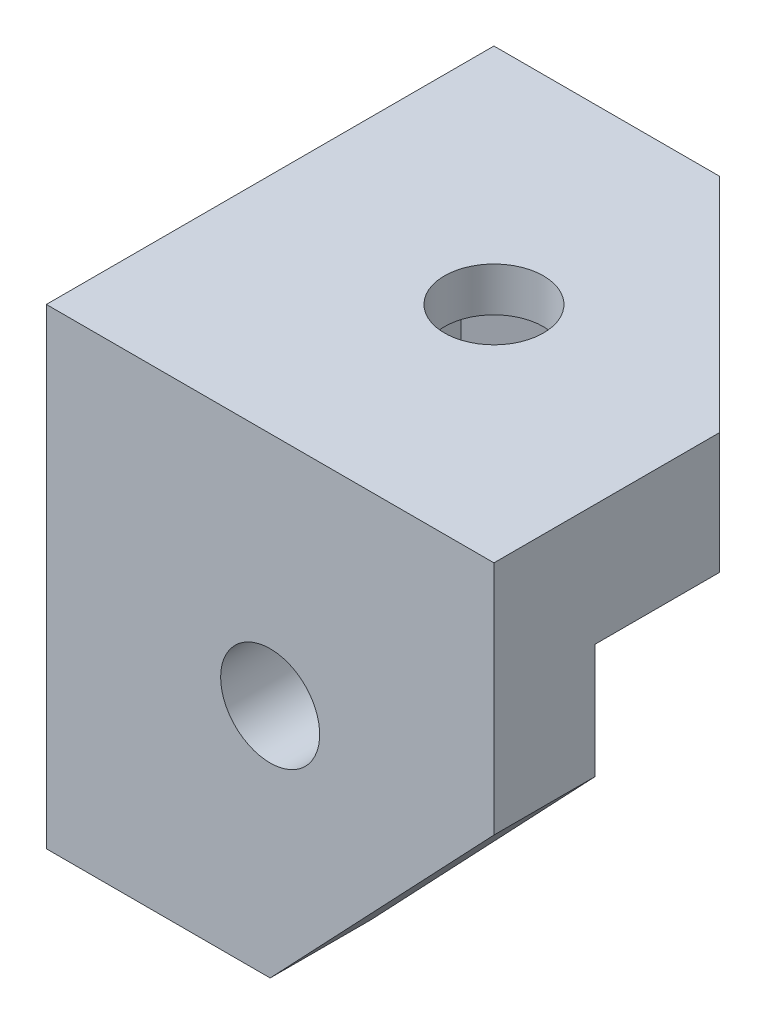
SolidWorks part; units mm, degrees
ref_plane "Front Plane" through (0, 0, 0) normal (0, 0, 1) x (1, 0, 0)
ref_plane "Top Plane" through (0, 0, 0) normal (0, 1, 0) x (1, 0, 0)
ref_plane "Right Plane" through (0, 0, 0) normal (1, 0, 0) x (0, 0, -1)
sketch "Sketch1" plane through (0, 0, 0) normal (0, 1, 0) x (1, 0, 0)
  line L1 (0, 0) -> (32.28, 0)
  line L5 (0, 0) -> (0, 32.28)
  line L6 (0, 32.28) -> (32.28, 32.28)
  line L8 (32.28, 32.28) -> (32.28, 0)
  dimension "D1" = 32.28
extrude "Main Body" add sketch "Sketch1" along normal blind 34
sketch "Sketch3" plane through (0, 0, 0) normal (0, 0, 1) x (1, 0, 0)
  line L0 (0, 0) -> (32.28, 34) construction
  circle A0 centre (16.14, 17) radius 3.5719
  circle A1 centre (16.14, 17) radius 7.9375 construction
  dimension "D1" = 7.1437
  dimension "D2" = 15.875
extrude "9/32 Right Rail" cut sketch "Sketch3" against normal blind 8.3344 and the other way through all
sketch "Sketch4" plane through (0, 0, 0) normal (-1, 0, 0) x (0, 0, 1)
  line L0 (0, 0) -> (-32.28, 34) construction
  circle A0 centre (-16.14, 17) radius 3.5719
  circle A1 centre (-16.14, 17) radius 7.9375 construction
  dimension "D1" = 7.1437
  dimension "D2" = 15.875
extrude "9/32 Left Rail" cut sketch "Sketch4" against normal blind 8.3344
sketch "Sketch8" plane through (0, 34, 0) normal (0, 1, 0) x (1, 0, 0)
  line L0 (0, 0) -> (32.28, 32.28) construction
  circle A0 centre (16.14, 16.14) radius 3.175 construction
  circle A1 centre (16.14, 16.14) radius 7.9375 construction
  circle A2 centre (16.14, 16.14) radius 3.5719
  dimension "D1" = 6.35
  dimension "D2" = 15.875
  dimension "D3" = 0.3969
extrude "9/32 Topper" cut sketch "Sketch8" against normal blind 10 and the other way through all
ref_plane "Plane1" through (5.5562, 0, 0) normal (-1, 0, 0) x (0, 0, 1)
sketch "Sketch9" plane through (0, 0, 0) normal (-1, 0, 0) x (0, 0, 1)
  line L0 (-16.14, 0) -> (-16.14, 34) construction
  line L1 (-9.7242, 17) -> (-12.9321, 22.5563) construction
  line L2 (-12.9321, 22.5563) -> (-19.3479, 22.5563) construction
  line L3 (-19.3479, 22.5563) -> (-22.5558, 17) construction
  line L4 (-22.5558, 17) -> (-19.3479, 11.4438) construction
  line L5 (-19.3479, 11.4438) -> (-12.9321, 11.4438) construction
  line L6 (-12.9321, 11.4438) -> (-9.7242, 17) construction
  line L7 (-32.28, 0) -> (0, 0) construction
  line L8 (-32.28, 34) -> (0, 34) construction
  line L9 (-19.4052, 22.6555) -> (-22.6704, 17)
  line L10 (-22.6704, 17) -> (-19.4052, 11.3445)
  line L11 (-19.4052, 11.3445) -> (-12.8748, 11.3445)
  line L12 (-12.8748, 11.3445) -> (-9.6096, 17)
  line L13 (-9.6096, 17) -> (-12.8748, 22.6555)
  line L14 (-12.8748, 22.6555) -> (-19.4052, 22.6555)
  line L15 (-32.28, 27.65) -> (-32.28, 6.35) construction
  line L16 (-32.28, 34) -> (-32.28, 0) construction
  line L17 (-32.28, 6.35) -> (-5.5562, 6.35) construction
  line L18 (-5.5562, 6.35) -> (-5.5562, 27.65) construction
  line L19 (-5.5562, 27.65) -> (-32.28, 27.65) construction
  line L20 (0, 34) -> (0, 0) construction
  circle A0 centre (-16.14, 17) radius 5.5563 construction
  point P15 (-16.14, 17)
  point P27 (-32.28, 17)
  point P29 (-32.28, 17)
  dimension "D1" = 11.1125
  dimension "D3" = 5.5562
  dimension "D4" = 6.35
  dimension "D2" = 0.0992
extrude "Hex Hole Right" [suppressed] cut sketch "Sketch9" against normal up to surface (26.7238 mm away) from surface up to face at (32.28, 17, -16.14) starting at plane "Plane1"
ref_plane "Plane2" through (0, 0, -5.5563) normal (0, 0, 1) x (1, 0, 0)
sketch "Sketch10" plane through (0, 0, 0) normal (0, 0, 1) x (1, 0, 0)
  line L0 (16.14, 0) -> (16.14, 34) construction
  line L1 (0, 0) -> (32.28, 0) construction
  line L2 (0, 34) -> (32.28, 34) construction
  line L3 (12.8748, 22.6555) -> (9.6096, 17)
  line L4 (22.5558, 17) -> (19.3479, 22.5562) construction
  line L5 (19.3479, 22.5562) -> (12.9321, 22.5562) construction
  line L6 (12.9321, 22.5562) -> (9.7242, 17) construction
  line L13 (9.7242, 17) -> (12.9321, 11.4438) construction
  line L14 (12.9321, 11.4438) -> (19.3479, 11.4438) construction
  line L15 (19.3479, 11.4438) -> (22.5558, 17) construction
  line L16 (9.6096, 17) -> (12.8748, 11.3445)
  line L17 (12.8748, 11.3445) -> (19.4052, 11.3445)
  line L18 (19.4052, 11.3445) -> (22.6704, 17)
  line L19 (22.6704, 17) -> (19.4052, 22.6555)
  line L20 (19.4052, 22.6555) -> (12.8748, 22.6555)
  circle A0 centre (16.14, 17) radius 5.5563 construction
  dimension "D1" = 11.1125
  dimension "D2" = 0.0992
extrude "Hex Hole Left" [suppressed] cut sketch "Sketch10" against normal up to surface (26.7238 mm away) from surface up to face at (16.14, 17, -32.28) starting at plane "Plane2"
sketch "Sketch13" plane through (0, 34, 0) normal (0, 1, 0) x (1, 0, 0)
  line L2 (32.28, 7.2926) -> (7.2926, 7.2926)
  line L3 (7.2926, 32.28) -> (7.2926, 7.2926)
  line L5 (32.28, 4.8617) -> (7.2926, 4.8617) construction
  line L7 (32.28, 32.28) -> (0, 32.28) construction
  line L8 (32.28, 0) -> (32.28, 32.28) construction
  line L9 (7.2926, 32.28) -> (32.28, 32.28)
  line L10 (32.28, 32.28) -> (32.28, 7.2926)
  line L11 (7.2926, 4.8617) -> (7.2926, 0) construction
  line L12 (0, 0) -> (32.28, 0) construction
  point P2 (11.1125, 5.5563)
  point P9 (32.28, 5.5563)
  dimension "D1" = 2.4309
  dimension "D2" = 4.8617
ref_plane "Plane4" through (0, 17, 0) normal (0, 1, 0) x (1, 0, 0)
extrude "Inner Cavity" cut sketch "Sketch13" along direction (0, -1, 0) on the side of the normal offset from surface 8.7312 and the other way up to surface (34 mm away) from surface up to face at (16.14, 34, -19.7119) other way up to face at (16.14, 0, -16.14) starting at plane "Plane4"
sketch "Sketch14" plane through (0, 34, 0) normal (0, 1, 0) x (1, 0, 0)
  line L0 (32.28, 0) -> (0, 32.28) construction
  line L1 (21.7955, 19.4052) -> (16.14, 22.6704)
  line L2 (21.6962, 19.3479) -> (16.14, 22.5558) construction
  line L3 (16.14, 22.5558) -> (10.5838, 19.3479) construction
  line L4 (10.5838, 19.3479) -> (10.5838, 12.9321) construction
  line L5 (10.5838, 12.9321) -> (16.14, 9.7242) construction
  line L6 (16.14, 9.7242) -> (21.6963, 12.9321) construction
  line L7 (21.6963, 12.9321) -> (21.6962, 19.3479) construction
  line L8 (16.14, 22.6704) -> (10.4845, 19.4052)
  line L9 (10.4845, 19.4052) -> (10.4845, 12.8748)
  line L10 (10.4845, 12.8748) -> (16.14, 9.6096)
  line L11 (16.14, 9.6096) -> (21.7955, 12.8748)
  line L12 (21.7955, 12.8748) -> (21.7955, 19.4052)
  line L14 (32.28, 32.28) -> (32.28, 7.2926) construction
  circle A0 centre (16.14, 16.14) radius 5.5562 construction
  dimension "D1" = 11.1125
  dimension "D2" = 0.0992
extrude "Hex Hole Top" cut sketch "Sketch14" along normal offset from surface (13.825 mm away) 3.175 from surface up to face at (16.14, 34, -19.7119) starting at plane "Plane4"
sketch "Sketch16" plane through (0, 34, 0) normal (0, 1, 0) x (1, 0, 0)
  line L0 (32.28, 32.28) -> (16.2767, 32.28)
  line L1 (32.28, 32.28) -> (0, 32.28) construction
  line L2 (16.2767, 32.28) -> (32.28, 16.2767)
  line L3 (32.28, 16.2767) -> (32.28, 32.28)
  line L4 (32.28, 0) -> (32.28, 32.28) construction
  circle A2 centre (16.14, 16.14) radius 3.5719 construction
  dimension "D1" = 7.9375
extrude "Top Corner" cut sketch "Sketch16" against normal up to next
sketch "Sketch17" plane through (0, 0, 0) normal (0, -1, 0) x (1, 0, 0)
  line L0 (32.28, -3.6463) -> (0, -3.6463) construction
  line L1 (32.28, 0) -> (32.28, -7.2926) construction
  line L2 (0, -32.28) -> (0, 0) construction
  line L3 (7.2926, -32.28) -> (0, -32.28) construction
  line L4 (3.6463, -32.28) -> (3.6463, 0) construction
  line L5 (0, 0) -> (32.28, 0) construction
  line L6 (4.44, -16.9337) -> (4.44, -15.3463) construction
  line L7 (16.9338, -2.8525) -> (15.3463, -2.8525)
  line L8 (16.9338, -2.8525) -> (16.9338, -4.44)
  line L9 (16.9338, -4.44) -> (15.3463, -4.44)
  line L10 (15.3463, -2.8525) -> (15.3463, -4.44)
  line L11 (16.9338, -2.8525) -> (15.3463, -4.44) construction
  line L12 (16.9338, -4.44) -> (15.3463, -2.8525) construction
  line L13 (4.44, -13.7588) -> (2.8525, -13.7588)
  line L14 (4.44, -13.7588) -> (4.44, -15.3463)
  line L15 (4.44, -15.3463) -> (2.8525, -15.3463)
  line L16 (2.8525, -13.7588) -> (2.8525, -15.3463)
  line L17 (4.44, -13.7588) -> (2.8525, -15.3463) construction
  line L18 (4.44, -15.3463) -> (2.8525, -13.7588) construction
  line L19 (4.44, -16.9337) -> (2.8525, -16.9337)
  line L20 (4.44, -16.9337) -> (4.44, -18.5213)
  line L21 (4.44, -18.5213) -> (2.8525, -18.5213)
  line L22 (2.8525, -16.9337) -> (2.8525, -18.5213)
  line L23 (4.44, -16.9337) -> (2.8525, -18.5213) construction
  line L24 (4.44, -18.5213) -> (2.8525, -16.9337) construction
  point P12 (16.14, -3.6463)
  point P17 (3.6463, -14.5525)
  point P22 (3.6463, -17.7275)
  point P27 (16.14, -3.6463)
  point P28 (3.6463, -16.14)
  point P29 (4.44, -16.14)
  dimension "D1" = 1.5875
  dimension "D2" = 1.5875
extrude "Cut-Extrude1" [suppressed] cut sketch "Sketch17" against normal blind 0.3969
sketch "Sketch18" plane through (0, 0, 0) normal (-1, 0, 0) x (0, 0, 1)
  line L0 (-32.28, 0) -> (-16.14, 0)
  line L1 (-32.28, 0) -> (0, 0) construction
  line L2 (-16.14, 0) -> (-32.28, 17)
  line L3 (-32.28, 34) -> (-32.28, 0) construction
  line L4 (-32.28, 17) -> (-32.28, 0)
  point P5 (0, 0)
  point P9 (-16.14, 0)
extrude "Cut-Extrude2" cut sketch "Sketch18" against normal up to surface (7.2926 mm away) up to face at (7.2926, 12.6344, -19.7863)
sketch "Sketch19" plane through (0, 0, 0) normal (0, 0, 1) x (1, 0, 0)
  line L0 (32.28, 0) -> (16.14, 0)
  line L1 (0, 0) -> (32.28, 0) construction
  line L2 (16.14, 0) -> (32.28, 17)
  line L3 (32.28, 34) -> (32.28, 0) construction
  line L4 (32.28, 17) -> (32.28, 0)
extrude "Cut-Extrude3" cut sketch "Sketch19" against normal up to surface (7.2926 mm away) up to face at (12.5681, 17, -7.2926)
